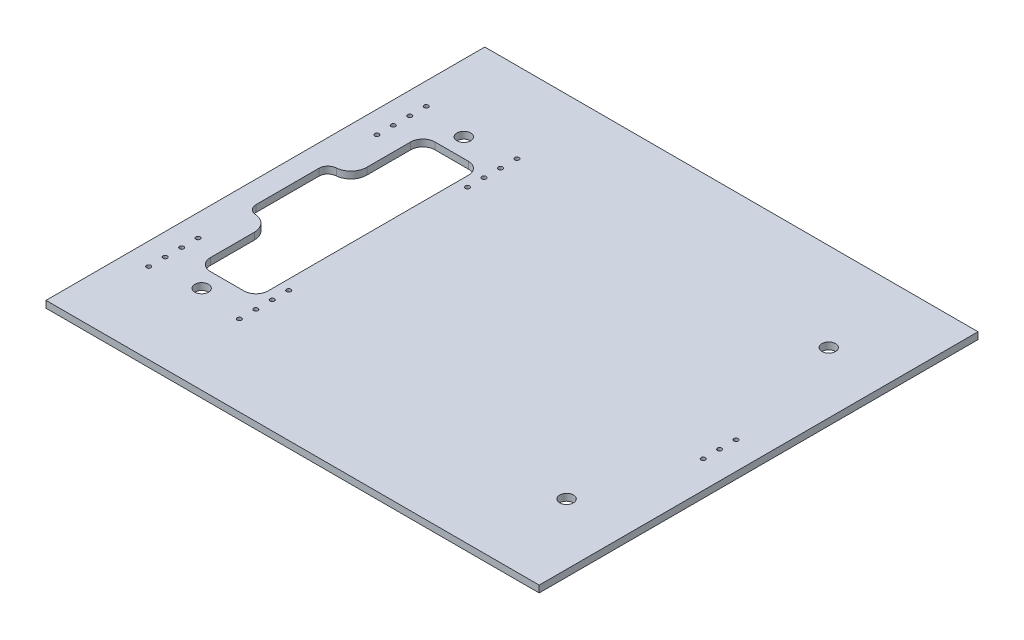
SolidWorks part; units mm, degrees
material "A-Glass Fiber"
ref_plane "Front Plane" through (0, 0, 0) normal (0, 0, 1) x (1, 0, 0)
ref_plane "Top Plane" through (0, 0, 0) normal (0, 1, 0) x (1, 0, 0)
ref_plane "Right Plane" through (0, 0, 0) normal (1, 0, 0) x (0, 0, -1)
sketch "Sketch1" plane through (0, 0, 0) normal (0, 1, 0) x (1, 0, 0)
  line L0 (0, 0) -> (57.817, 0) construction
  line L1 (-56.3773, -50.8) -> (57.817, -50.8)
  line L2 (-56.3773, -50.8) -> (-56.3773, 50.8)
  line L3 (-56.3773, 50.8) -> (57.817, 50.8)
  line L4 (57.817, -50.8) -> (57.817, 50.8)
  line L5 (-56.3773, -50.8) -> (57.817, 50.8) construction
  line L6 (-56.3773, 50.8) -> (57.817, -50.8) construction
  point P0 (0.7199, 0)
  dimension "D1" = 101.6
extrude "Boss-Extrude1" add sketch "Sketch1" against normal blind 1.5875
sketch "Sketch2" plane through (0, 0, 0) normal (0, 1, 0) x (1, 0, 0)
  circle A1 centre (-51.2705, 24.505) radius 0.5
  circle A2 centre (-51.2705, 24.505) radius 0.5
  circle A3 centre (-30.2705, 28.315) radius 0.5
  circle A4 centre (-30.2705, 28.315) radius 0.5
  circle A5 centre (-30.2705, 32.125) radius 0.5
  circle A6 centre (-30.2705, 32.125) radius 0.5
  circle A7 centre (-30.2704, -32.135) radius 0.5
  circle A8 centre (-30.2704, -32.135) radius 0.5
  circle A9 centre (-30.2704, -28.325) radius 0.5
  circle A10 centre (-30.2704, -28.325) radius 0.5
  circle A11 centre (-30.2704, -24.515) radius 0.5
  circle A12 centre (-30.2704, -24.515) radius 0.5
  circle A13 centre (-30.2705, -20.705) radius 0.5
  circle A14 centre (-30.2705, -20.705) radius 0.5
  circle A15 centre (51.4795, -6.483) radius 0.5
  circle A16 centre (51.4795, -6.483) radius 0.5
  circle A17 centre (51.4795, -2.673) radius 0.5
  circle A18 centre (51.4795, -2.673) radius 0.5
  circle A19 centre (-51.2705, 28.315) radius 0.5
  circle A20 centre (-51.2705, 28.315) radius 0.5
  circle A21 centre (-51.2705, 32.125) radius 0.5
  circle A22 centre (-51.2705, 32.125) radius 0.5
  circle A23 centre (-51.2704, -32.135) radius 0.5
  circle A24 centre (-51.2704, -32.135) radius 0.5
  circle A25 centre (-51.2704, -28.325) radius 0.5
  circle A26 centre (-51.2704, -28.325) radius 0.5
  circle A27 centre (-51.2704, -24.515) radius 0.5
  circle A28 centre (-51.2704, -24.515) radius 0.5
  circle A29 centre (-51.2704, -20.705) radius 0.5
  circle A30 centre (-51.2704, -20.705) radius 0.5
  circle A31 centre (-30.2705, 20.695) radius 0.5
  circle A32 centre (-30.2705, 20.695) radius 0.5
  circle A33 centre (-30.2705, 24.505) radius 0.5
  circle A34 centre (-30.2705, 24.505) radius 0.5
  circle A35 centre (-40.7894, -30.35) radius 1.5875
  circle A36 centre (-40.7894, -30.35) radius 1.5875
  circle A37 centre (-40.7894, 30.35) radius 1.5875
  circle A38 centre (-40.7894, 30.35) radius 1.5875
  circle A39 centre (43.7106, 30.35) radius 1.5875
  circle A40 centre (43.7106, 30.35) radius 1.5875
  circle A41 centre (43.7106, -30.35) radius 1.5875
  circle A42 centre (43.7106, -30.35) radius 1.5875
  circle A43 centre (51.4795, 1.137) radius 0.5
  circle A44 centre (51.4795, 1.137) radius 0.5
  circle A45 centre (-51.2705, 20.695) radius 0.5
  circle A46 centre (-51.2705, 20.695) radius 0.5
  dimension "D10" = 0
  dimension "D11" = 0
  dimension "D12" = 0
  dimension "D13" = 0
  dimension "D14" = 0
  dimension "D15" = 0
  dimension "D16" = 0
  dimension "D17" = 0
  dimension "D18" = 0
  dimension "D19" = 0
  dimension "D20" = 0
  dimension "D21" = 0
  dimension "D22" = 0
  dimension "D23" = 0
  dimension "D24" = 0
  dimension "D25" = 0
  dimension "D26" = 0
  dimension "D27" = 0
  dimension "D28" = 0
  dimension "D29" = 0
  dimension "D30" = 0
  dimension "D31" = 0
  dimension "D32" = 0
extrude "Cut-Extrude1" cut sketch "Sketch2" against normal through all
sketch "Sketch3" plane through (0, 0, 0) normal (0, 1, 0) x (1, 0, 0)
  line L0 (-51.2627, -7.3042) -> (-51.2627, 7.3042)
  line L5 (-56.3773, 0) -> (0, 0) construction
  line L7 (-49.9829, -3.75) -> (-51.2627, -3.75) construction
  line L8 (-56.3773, 50.8) -> (-56.3773, -50.8) construction
  line L10 (-49.2428, 9.324) -> (-49.6148, 9.324)
  line L11 (-49.2428, -9.324) -> (-49.6148, -9.324)
  line L12 (-45.9191, 13.0197) -> (-45.9191, 23.1948)
  line L13 (-45.9191, -13.0197) -> (-45.9191, -23.1948)
  line L14 (-43.1203, 25.9936) -> (-35.359, 25.9936)
  line L15 (-43.1203, -25.9936) -> (-35.359, -25.9936)
  line L16 (-32.5602, 23.1948) -> (-32.5602, -23.1948)
  arc A3 (-49.2428, -9.324) -> (-51.2627, -7.3042) centre (-49.2428, -7.3042) cw
  arc A5 (-45.9191, 23.1948) -> (-43.1203, 25.9936) centre (-43.1203, 23.1948) cw
  arc A6 (-45.9191, -23.1948) -> (-43.1203, -25.9936) centre (-43.1203, -23.1948) ccw
  arc A7 (-35.359, 25.9936) -> (-32.5602, 23.1948) centre (-35.359, 23.1948) cw
  arc A8 (-35.359, -25.9936) -> (-32.5602, -23.1948) centre (-35.359, -23.1948) ccw
  arc A9 (-45.9191, 13.0197) -> (-49.6148, 9.324) centre (-49.6148, 13.0197) cw
  arc A10 (-45.9191, -13.0197) -> (-49.6148, -9.324) centre (-49.6148, -13.0197) ccw
  arc A11 (-49.2428, 9.324) -> (-51.2627, 7.3042) centre (-49.2428, 7.3042) ccw
  arc A12 (-49.5829, -2.15) -> (-49.5829, -5.35) centre (-46.5829, -3.75) ccw construction
  point P24 (-32.5602, 0)
  point P31 (-51.2627, 0)
extrude "Cut-Extrude2" cut sketch "Sketch3" against normal through all
equation "\"62.5mi\"=0.1"
